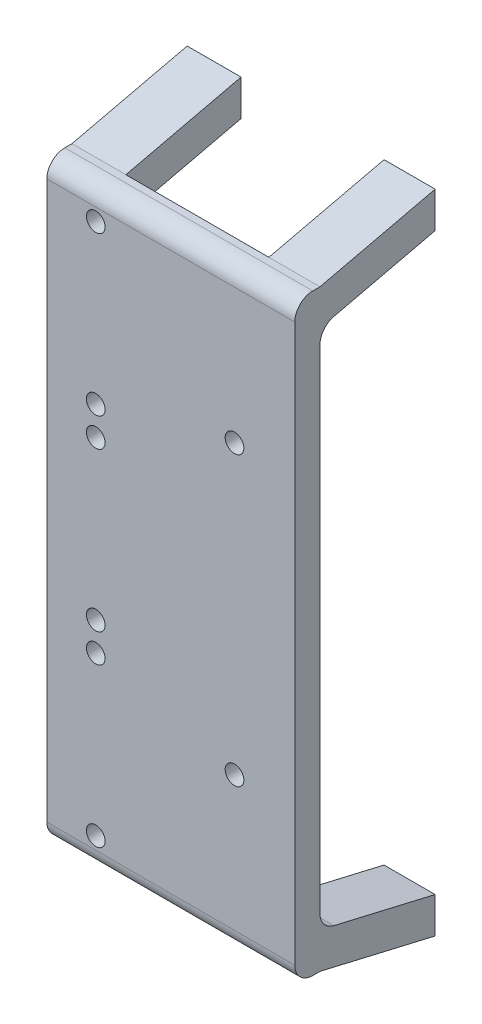
SolidWorks part; units mm, degrees
ref_plane "Front Plane" through (0, 0, 0) normal (0, 0, 1) x (1, 0, 0)
ref_plane "Top Plane" through (0, 0, 0) normal (0, 1, 0) x (1, 0, 0)
ref_plane "Right Plane" through (0, 0, 0) normal (1, 0, 0) x (0, 0, -1)
sketch "Sketch1" plane through (0, 0, 0) normal (0, 0, 1) x (1, 0, 0)
  line L1 (57.6604, -68.1714) -> (126.6604, -68.1714)
  line L2 (57.6604, -68.1714) -> (57.6604, 96.8286)
  line L3 (57.6604, 96.8286) -> (126.6604, 96.8286)
  line L4 (126.6604, -68.1714) -> (126.6604, 96.8286)
  line L5 (57.6604, -68.1714) -> (126.6604, 96.8286) construction
  line L6 (57.6604, 96.8286) -> (126.6604, -68.1714) construction
  point P0 (92.1604, 14.3286)
  dimension "D1" = 69
  dimension "D2" = 165
extrude "Boss-Extrude1" add sketch "Sketch1" along normal blind 7
ref_plane "Plane1" through (0, 14.3286, 0) normal (0, -1, 0) x (-1, 0, 0)
sketch "Sketch3" plane through (0, 0, 7) normal (0, 0, 1) x (1, 0, 0)
  line L0 (109.8833, -25.6714) -> (109.8833, 54.3286) construction
  line L2 (126.6604, -68.1714) -> (126.6604, 96.8286) construction
  circle A0 centre (109.8833, 54.3286) radius 2.6
  circle A1 centre (109.8833, -25.6714) radius 2.6
  point P5 (126.6604, 14.3286)
  point P6 (109.8833, 14.3286)
  dimension "D2" = 5.2
  dimension "D3" = 5.2
  dimension "D1" = 80
extrude "Cut-Extrude2" cut sketch "Sketch3" against normal up to surface (7 mm away) up to face at (92.1604, 14.3286, 0)
sketch "Sketch4" plane through (126.6604, 0, 0) normal (1, 0, 0) x (0, 0, -1)
  line L0 (0, -68.1714) -> (32.0586, -75.6714)
  line L5 (32.0586, 100.8786) -> (32.0586, 96.8786) construction
  line L6 (32.0586, -75.6714) -> (32.0586, -65.6714)
  line L7 (32.0586, -65.6714) -> (0, -58.1714)
  line L8 (0, -68.1714) -> (0, 96.8286) construction
  line L9 (0, -58.1714) -> (0, -68.1714)
  dimension "D1" = 10
extrude "Boss-Extrude2" add sketch "Sketch4" against normal up to surface (69 mm away) up to face at (57.6604, 14.3286, 3.5)
sketch "Sketch7" plane through (0, 0, -32.0586) normal (0, 0, -1) x (-1, 0, 0)
  circle A0 centre (-119.4466, -70.2214) radius 2.6
  circle A1 centre (-65.6466, -70.2214) radius 2.6
  dimension "D1" = 5.2
  dimension "D2" = 5.2
extrude "Cut-Extrude3" cut sketch "Sketch7" against normal blind 7
sketch "Sketch8" plane through (0, 0, -32.0586) normal (0, 0, -1) x (-1, 0, 0)
  line L1 (-112.4466, -35.9928) -> (-72.6466, -35.9928)
  line L2 (-112.4466, -35.9928) -> (-112.4466, -85.9928)
  line L3 (-112.4466, -85.9928) -> (-72.6466, -85.9928)
  line L4 (-72.6466, -35.9928) -> (-72.6466, -85.9928)
  line L5 (-112.4466, -35.9928) -> (-72.6466, -85.9928) construction
  line L6 (-112.4466, -85.9928) -> (-72.6466, -35.9928) construction
  circle A0 centre (-119.4466, -70.2214) radius 2.6 construction
  circle A1 centre (-65.6466, -70.2214) radius 2.6 construction
  point P0 (-92.5466, -60.9928)
  dimension "D1" = 7
  dimension "D2" = 7
  dimension "D3" = 50
extrude "Cut-Extrude4" cut sketch "Sketch8" against normal up to surface (32.0586 mm away) up to face at (92.1604, 19.3286, 0)
mirror "Mirror7" about plane through (0, 14.3286, 0) normal (0, -1, 0) of "Cut-Extrude4", "Cut-Extrude3", "Boss-Extrude2"
fillet "Fillet4" radius 5 4 edges at (119.5535, -58.1714, 0) (65.1535, -58.1714, 0) (65.1535, 86.8286, 0) (119.5535, 86.8286, 0)
fillet "Fillet5" radius 5 2 edges at (92.1604, 96.8286, 7) (92.1604, -68.1714, 7)
sketch "Sketch2" plane through (0, 0, 7) normal (0, 0, 1) x (1, 0, 0)
  line L0 (71.2675, -59.6714) -> (71.2675, -15.6714) construction
  line L1 (71.2675, -7.6714) -> (71.2675, 36.3286) construction
  line L2 (71.2675, 44.3286) -> (71.2675, 88.3286) construction
  line L3 (57.6604, 91.8286) -> (57.6604, -63.1714) construction
  circle A0 centre (71.2675, -59.6714) radius 2.6
  circle A1 centre (71.2675, -15.6714) radius 2.6
  circle A2 centre (71.2675, -7.6714) radius 2.6
  circle A3 centre (71.2675, 36.3286) radius 2.6
  circle A4 centre (71.2675, 44.3286) radius 2.6
  circle A5 centre (71.2675, 88.3286) radius 2.6
  point P14 (57.6604, 14.3286)
  point P15 (71.2675, 14.3286)
  dimension "D2" = 5.2
  dimension "D3" = 5.2
  dimension "D5" = 5.2
  dimension "D6" = 5.2
  dimension "D8" = 5.2
  dimension "D9" = 5.2
  dimension "D1" = 44
  dimension "D4" = 44
  dimension "D7" = 44
  dimension "D10" = 8
  dimension "D11" = 8
extrude "Cut-Extrude1" cut sketch "Sketch2" against normal up to surface (7 mm away) up to face at (92.4179, 14.3286, 0)
